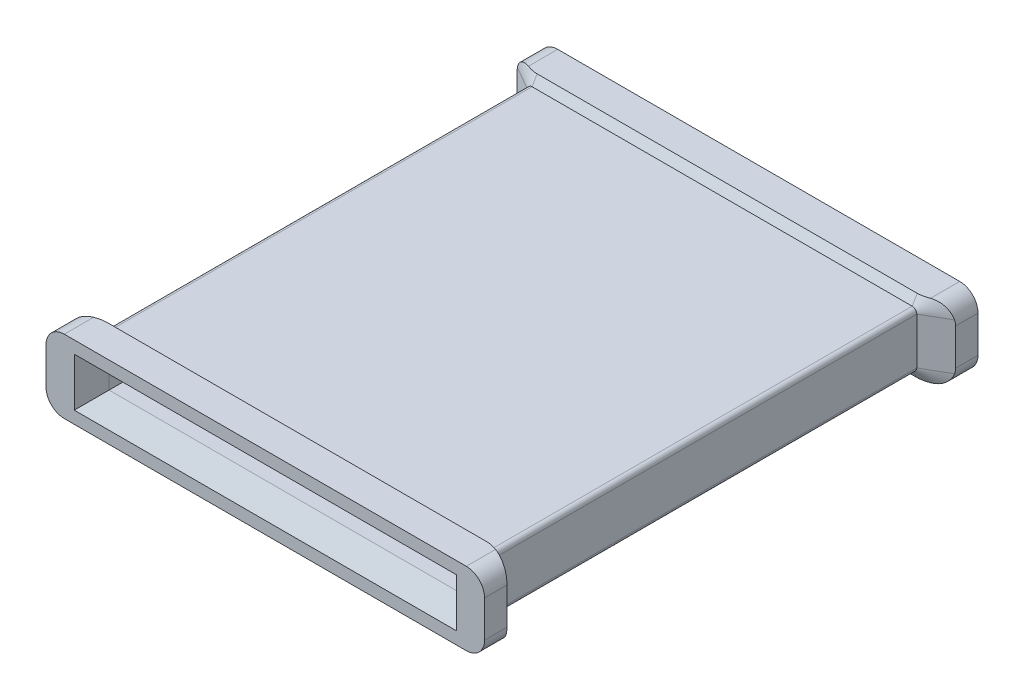
SolidWorks part; units mm, degrees
material "ABS"
ref_plane "Front Plane" through (0, 0, 0) normal (0, 0, 1) x (1, 0, 0)
ref_plane "Top Plane" through (0, 0, 0) normal (0, 1, 0) x (1, 0, 0)
ref_plane "Right Plane" through (0, 0, 0) normal (1, 0, 0) x (0, 0, -1)
sketch "Sketch1" plane through (0, 0, 0) normal (0, 0, 1) x (1, 0, 0)
  line L0 (0, 8) -> (48, 8)
  line L3 (48, 8) -> (48, 0)
  line L4 (48, 0) -> (0, 0)
  line L5 (0, 0) -> (0, 8)
  line L9 (3.4, 6.35) -> (44.6, 6.35)
  line L10 (3.4, 6.35) -> (3.4, 1.65)
  line L11 (3.4, 1.65) -> (44.6, 1.65)
  line L12 (44.6, 6.35) -> (44.6, 1.65)
  dimension "D1" = 1.65
  dimension "D2" = 41.2
  dimension "D4" = 4.7
  dimension "D5" = 1.65
  dimension "D7" = 3.4
  dimension "D8" = 3.4
extrude "Boss-Extrude1" add sketch "Sketch1" along normal blind 54
sketch "Sketch2" plane through (0, 0, 54) normal (0, 0, 1) x (1, 0, 0)
  line L1 (3.2, 7.05) -> (44.8, 7.05)
  line L2 (2.7, 6.55) -> (2.7, 1.45)
  line L3 (3.2, 0.95) -> (44.8, 0.95)
  line L4 (45.3, 6.55) -> (45.3, 1.45)
  line L5 (3.4, 1.65) -> (44.6, 1.65) construction
  line L6 (44.6, 6.35) -> (3.4, 6.35) construction
  line L8 (3.4, 6.35) -> (3.4, 1.65) construction
  line L9 (44.6, 1.65) -> (44.6, 6.35) construction
  arc A0 (2.7, 1.45) -> (3.2, 0.95) centre (3.2, 1.45) ccw
  arc A1 (44.8, 0.95) -> (45.3, 1.45) centre (44.8, 1.45) ccw
  arc A2 (44.8, 7.05) -> (45.3, 6.55) centre (44.8, 6.55) cw
  arc A3 (3.2, 7.05) -> (2.7, 6.55) centre (3.2, 6.55) ccw
  dimension "D1" = 0.5
  dimension "D2" = 0.7
  dimension "D3" = 0.7
  dimension "D4" = 0.7
  dimension "D5" = 0.7
extrude "Cut-Extrude1" cut sketch "Sketch2" against normal offset from surface (50 mm away) 2 from offset 2 flip side to cut up to face at (24, 4, 0) offset against normal yes
fillet "Fillet1" radius 2 8 edges at (48, 8, 53) (48, 0, 53) (48, 0, 1) (48, 8, 1) (0, 0, 1) (0, 8, 1) (0, 0, 53) (0, 8, 53)
chamfer "Chamfer4" distance 2 angle 60 16 edges at (2.7, 4, 52) (2.8464, 1.0964, 52) (2.8464, 6.9036, 52) (24, 0.95, 52) (24, 7.05, 52) (45.1536, 1.0964, 52) (45.1536, 6.9036, 52) (45.3, 4, 52) (2.7, 4, 2) (2.8464, 1.0964, 2) (2.8464, 6.9036, 2) (24, 0.95, 2) (24, 7.05, 2) (45.1536, 1.0964, 2) (45.1536, 6.9036, 2) (45.3, 4, 2) first distance on face at (2.7, 4, 27) first distance on face at (2.8982, 1.1482, 27) first distance on face at (2.8982, 6.8518, 27) first distance on face at (24, 0.95, 27) first distance on face at (24, 7.05, 27) first distance on face at (45.1018, 1.1482, 27) first distance on face at (45.1018, 6.8518, 27) first distance on face at (45.3, 4, 27)
chamfer "Chamfer5" distance 3.5 angle 5 8 edges at (44.6, 4, 54) (24, 1.65, 54) (3.4, 4, 54) (24, 6.35, 54) (44.6, 4, 0) (24, 1.65, 0) (3.4, 4, 0) (24, 6.35, 0) first distance on face at (44.6, 4, 27) first distance on face at (24, 1.65, 27) first distance on face at (3.4, 4, 27) first distance on face at (24, 6.35, 27)
